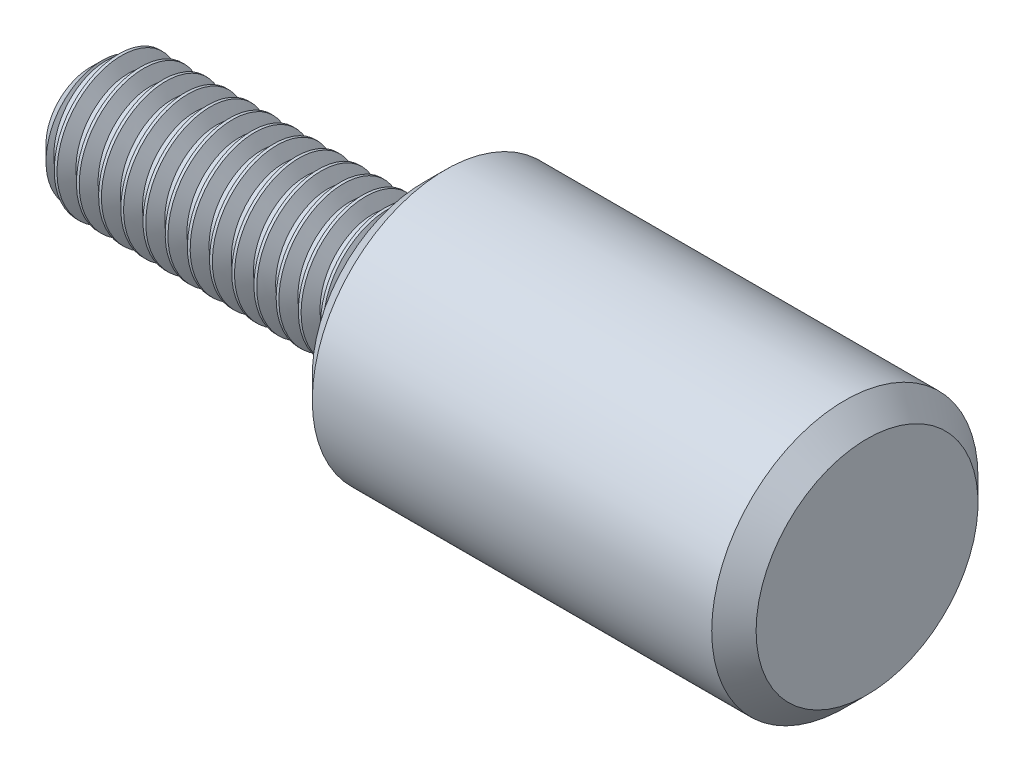
SolidWorks part; units mm, degrees
material "AISI 1020"
ref_plane "Front Plane" through (0, 0, 0) normal (0, 0, 1) x (1, 0, 0)
ref_plane "Top Plane" through (0, 0, 0) normal (0, 1, 0) x (1, 0, 0)
ref_plane "Right Plane" through (0, 0, 0) normal (1, 0, 0) x (0, 0, -1)
sketch "Sketch1" plane through (0, 0, 0) normal (0, 0, 1) x (1, 0, 0)
  line L0 (0, 0) -> (35, 0) construction
  line L1 (0, 3) -> (15, 3)
  line L2 (15, 3) -> (15, 6)
  line L3 (15, 6) -> (35, 6)
  line L4 (35, 6) -> (35, 0)
  line L5 (0, 3) -> (0, 0)
  line L6 (0, 0) -> (35, 0)
  dimension "D1" = 35
  dimension "D2" = 6
  dimension "D3" = 12
  dimension "D4" = 15
revolve "Revolve1" add sketch "Sketch1" angle 360 about L0
chamfer "Chamfer1" distance 1 angle 45 2 edges at (35, 0, 6) (15, 0, 6)
chamfer "Chamfer2" distance 1 angle 45 1 edges at (0, 0, 3)
thread "Thread1" pitch 1 method cut trim with end face yes profile "Thread Profile1" start angle 0, offset 2, length 0, pitch 1, diameter 6
ref_plane "Plane1" through (-1, 0, -3) normal (0, -1, 0) x (0, 0, -1)
sketch "Thread Profile1" plane through (-1, 0, -3) normal (0, -1, 0) x (0, 0, -1)
  line L0 (0, 0) -> (0, 1) construction
  line L11 (0, 0) -> (0, 0.875)
  line L12 (0, 0.875) -> (-0.5413, 0.5625)
  line L13 (-0.5413, 0.5625) -> (-0.5413, 0.3125)
  line L15 (-0.5413, 0.3125) -> (0, 0)
  line L17 (-0.5413, 0.4375) -> (0, 0.4375) construction
  point P2 (0, 0)
  dimension "Pitch" = 1
  dimension "Profile_Angle" = 60
  dimension "Profile_Land" = 0.25
  dimension "Profile_Height" = 0.5413
